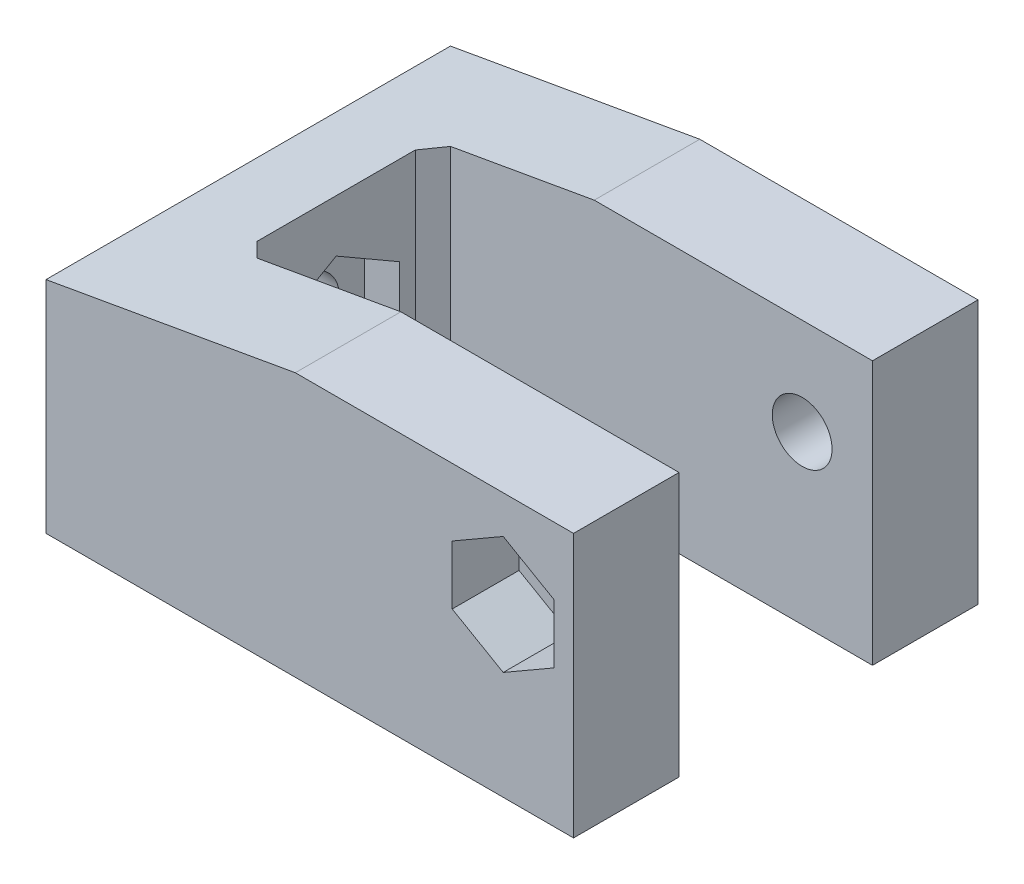
SolidWorks part; units mm, degrees
ref_plane "Front Plane" through (0, 0, 0) normal (0, 0, 1) x (1, 0, 0)
ref_plane "Top Plane" through (0, 0, 0) normal (0, 1, 0) x (1, 0, 0)
ref_plane "Right Plane" through (0, 0, 0) normal (1, 0, 0) x (0, 0, -1)
sketch "Sketch1" plane through (0, 0, 0) normal (1, 0, 0) x (0, 0, -1)
  line L1 (0, 0) -> (23, 0)
  line L2 (0, 0) -> (0, 15)
  line L3 (0, 15) -> (23, 15)
  line L4 (23, 0) -> (23, 15)
  dimension "D1" = 23
  dimension "D2" = 15
extrude "Boss-Extrude1" add sketch "Sketch1" along normal blind 30
sketch "Sketch2" plane through (30, 0, 0) normal (1, 0, 0) x (0, 0, -1)
  line L0 (11.5, 15) -> (11.5, 0) construction
  line L1 (6, 15) -> (17, 15)
  line L2 (6, 15) -> (6, 0)
  line L3 (6, 0) -> (17, 0)
  line L4 (17, 15) -> (17, 0)
  line L5 (0, 0) -> (23, 0) construction
  line L8 (23, 15) -> (0, 15) construction
  line L9 (11.5, 15) -> (11.5, 0) construction
  dimension "D1" = 11
extrude "Cut-Extrude1" cut sketch "Sketch2" against normal offset from surface (25 mm away) 5 up to face at (0, 7.5, -11.5)
sketch "Sketch3" plane through (0, 0, -23) normal (0, 0, -1) x (-1, 0, 0)
  line L1 (-30, 0) -> (-30, 15) construction
  line L2 (-30, 0) -> (0, 0) construction
  circle A0 centre (-26, 9.5) radius 1.7
  dimension "D3" = 3.4
  dimension "D1" = 9.5
  dimension "D2" = 4
extrude "Cut-Extrude2" cut sketch "Sketch3" against normal through all both and the other way through all
chamfer "Chamfer1" distance 2.5 angle 80 1 edges at (0, 15, -11.5) first distance on face at (0, 7.5, -11.5)
sketch "Sketch4" plane through (0, 0, 0) normal (-1, 0, 0) x (0, 0, 1)
  line L0 (-11.5, 12.5) -> (-11.5, 0) construction
  line L1 (0, 12.5) -> (-23, 12.5) construction
  line L2 (0, 0) -> (-23, 0) construction
  line L3 (-23, 6.25) -> (0, 6.25) construction
  line L4 (-23, 0) -> (-23, 12.5) construction
  line L5 (0, 12.5) -> (0, 0) construction
  circle A0 centre (-11.5, 6.25) radius 2.2
  dimension "D1" = 4.4
extrude "Cut-Extrude3" cut sketch "Sketch4" against normal blind 10
sketch "Sketch5" plane through (5, 0, 0) normal (1, 0, 0) x (0, 0, -1)
  line L1 (7.9, 8.3285) -> (7.9, 4.1715)
  line L2 (7.9, 4.1715) -> (11.5, 2.0931)
  line L3 (11.5, 2.0931) -> (15.1, 4.1715)
  line L4 (15.1, 4.1715) -> (15.1, 8.3285)
  line L5 (15.1, 8.3285) -> (11.5, 10.4069)
  line L6 (11.5, 10.4069) -> (7.9, 8.3285)
  circle A0 centre (11.5, 6.25) radius 3.6 construction
  dimension "D1" = 7.2
extrude "Cut-Extrude4" cut sketch "Sketch5" against normal blind 2
sketch "Sketch6" plane through (0, 0, -23) normal (0, 0, -1) x (-1, 0, 0)
  circle A0 centre (-26, 9.5) radius 3.25
  dimension "D1" = 6.5
extrude "Cut-Extrude5" cut sketch "Sketch6" against normal blind 2.5
sketch "Sketch7" plane through (0, 0, 0) normal (0, 0, 1) x (1, 0, 0)
  line L1 (23.1, 11.1743) -> (23.1, 7.8257)
  line L2 (23.1, 7.8257) -> (26, 6.1514)
  line L3 (26, 6.1514) -> (28.9, 7.8257)
  line L4 (28.9, 7.8257) -> (28.9, 11.1743)
  line L5 (28.9, 11.1743) -> (26, 12.8486)
  line L6 (26, 12.8486) -> (23.1, 11.1743)
  circle A0 centre (26, 9.5) radius 2.9 construction
  dimension "D1" = 5.8
extrude "Cut-Extrude6" cut sketch "Sketch7" against normal blind 3.8
sketch "Sketch8" plane through (0, 0, -17) normal (0, 0, 1) x (1, 0, 0)
  circle A0 centre (26, 9.5) radius 2.1
  circle A1 centre (26, 9.5) radius 1.6009
  dimension "D1" = 4.2
  dimension "D2" = 3.2017
sketch "Sketch9" plane through (0, 0, -6) normal (0, 0, -1) x (-1, 0, 0)
  circle A0 centre (-26, 9.5) radius 1.6
  circle A1 centre (-26, 9.5) radius 2.1
  dimension "D1" = 4.2
  dimension "D2" = 3.2
chamfer "Chamfer3" distance 1 angle 45 2 edges at (5, 6.6908, -6) (5, 6.6908, -17)
